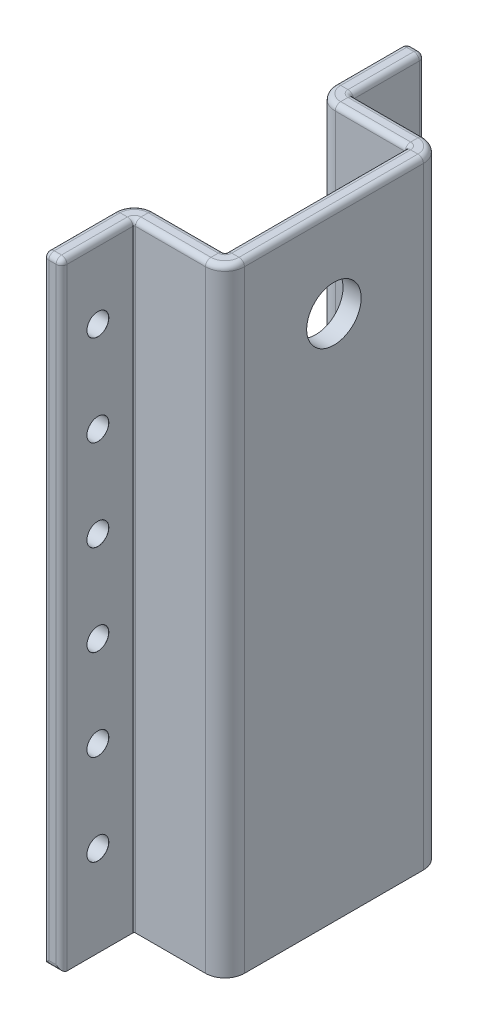
SolidWorks part; units mm, degrees
note: The reader was unsure of these and kept them because the rebuilt part matched: flange length of "Edge-Flange1", "Edge-Flange2".
material "1.0037 (S235JR)"
ref_plane "Front Plane" through (0, 0, 0) normal (0, 0, 1) x (1, 0, 0)
ref_plane "Top Plane" through (0, 0, 0) normal (0, 1, 0) x (1, 0, 0)
ref_plane "Right Plane" through (0, 0, 0) normal (1, 0, 0) x (0, 0, -1)
sketch "Sketch1" plane through (0, 0, 0) normal (1, 0, 0) x (0, 0, -1)
  line L1 (-60, 170) -> (60, 170)
  line L2 (-60, 170) -> (-60, -170)
  line L3 (-60, -170) -> (60, -170)
  line L4 (60, 170) -> (60, -170)
  point P6 (0, 170)
  point P7 (60, 0)
  dimension "D1" = 340
  dimension "D2" = 120
base flange "Base-Flange1" sketch "Sketch1" thickness 10 reverse thickness direction yes parameters "D1"=0.7366
edge flange "Edge-Flange1" sketch "Sketch10" flange profiles "Sketch10", "Sketch11" flange angle 90 flange length 60 flange position material inside bend radius 0.7366 thickness 10 relief rectangular parameters "D6"=10, "D8"=1
sketch "Sketch10" plane through (0, 0, 60) normal (0, 0, 1) x (0, 1, 0)
  line L2 (-170, 0) -> (-170, 50)
  line L3 (-170, 50) -> (170, 50)
  line L4 (170, 50) -> (170, 0)
  line L11 (170, 0) -> (-170, 0) construction
  line L12 (170, 0) -> (-170, 0)
sketch "Sketch11" plane through (0, 0, -60) normal (0, 0, -1) x (0, -1, 0)
  line L0 (170, 0) -> (-170, 0) construction
  line L1 (170, 0) -> (-170, 0)
  line L2 (-170, 0) -> (-170, 50)
  line L3 (-170, 50) -> (170, 50)
  line L4 (170, 50) -> (170, 0)
bend "EdgeBend1" bend radius 0.7366 bend angle 90 parameters "D5"=1
bend "EdgeBend2" bend radius 0.7366 bend angle 90 parameters "D5"=2
edge flange "Edge-Flange2" sketch "Sketch16" flange profiles "Sketch16", "Sketch17" flange angle 90 flange length 40 flange position material inside bend radius 0.7366 thickness 10 relief rectangular parameters "D6"=10, "D8"=1
sketch "Sketch16" plane through (-50, 0, 60) normal (-1, 0, 0) x (0, -1, 0)
  line L2 (-170, 0) -> (-170, 40)
  line L3 (-170, 40) -> (170, 40)
  line L4 (170, 40) -> (170, 0)
  line L7 (-170, 0) -> (170, 0) construction
  line L8 (-170, 0) -> (170, 0)
sketch "Sketch17" plane through (-50, 0, -60) normal (-1, 0, 0) x (0, 1, 0)
  line L0 (-170, 0) -> (170, 0) construction
  line L1 (-170, 0) -> (170, 0)
  line L2 (-170, 0) -> (-170, 40)
  line L3 (-170, 40) -> (170, 40)
  line L4 (170, 40) -> (170, 0)
bend "EdgeBend3" bend radius 0.7366 bend angle 90 parameters "D5"=3
bend "EdgeBend4" bend radius 0.7366 bend angle 90 parameters "D5"=4
sketch "Sketch18" plane through (10, 0, 0) normal (1, 0, 0) x (0, 0, -1)
  line L0 (-100, -170) -> (-100, 170) construction
  line L5 (49.2634, 170) -> (-49.2634, 170) construction
  circle A0 centre (0, 120) radius 15
  dimension "D1" = 30
  dimension "D3" = 100
  dimension "D2" = 50
extrude "Cut-Extrude1" cut sketch "Sketch18" against normal through all normal cut yes
hole_wizard "M10 Clearance Hole1" positions "Sketch19" profile "Sketch20" hole size "M10" standard "ANSI Metric" end condition through all
sketch "Sketch19" plane through (-40, 0, 0) normal (1, 0, 0) x (0, 0, -1)
  line L0 (100, 170) -> (100, -170) construction
  line L1 (100, -170) -> (60.7366, -170) construction
  point P0 (80, -120)
  point P2 (80, -70)
  point P4 (80, -20)
  point P6 (80, 30)
  point P8 (80, 80)
  point P10 (80, 130)
  dimension "D1" = 20
  dimension "D2" = 50
  dimension "D3" = 50
  dimension "D4" = 50
  dimension "D5" = 50
  dimension "D6" = 50
  dimension "D7" = 50
sketch "Sketch20" plane through (-40, -120, -80) normal (0, 1, 0) x (0, 0, -1)
  line L0 (0, 0) -> (0, 10)
  line L1 (0, 10) -> (6, 10)
  line L2 (6, 10) -> (6, 0.025)
  line L3 (6, 0.025) -> (6.025, 0)
  line L5 (6.025, 0) -> (0, 0)
  line L6 (-6, 0.025) -> (-6.025, 0) construction
  line L11 (0, -6.35) -> (0, 107.95) construction
  dimension "Thru Hole Dia." = 12
  dimension "Thru Hole Depth" = 10
  dimension "Near C'Sink Dia." = 12.05
  dimension "Near C'Sink Angle" = 90
mirror "Mirror1" about plane through (0, 0, 0) normal (0, 0, 1) of "M10 Clearance Hole1"
fillet "Fillet1" radius 3 26 edges at (-46.8553, 170, 53.1447) (-39.7843, 170, 60.2157) (-45, 170, 100) (-40, 170, 80.3683) (-50, 0, 100) (-50, 170, 80.3683) (-40, 0, 100) (-45, -170, 100) (-46.8553, 170, -53.1447) (-39.7843, 170, -60.2157) (-45, -170, -100) (-40, 170, -80.3683) (-50, 170, -80.3683) (-50, 0, -100) (-40, 0, -100) (-45, 170, -100) (0, 170, 0) (10, 170, 0) (6.8553, 170, 56.8553) (-0.2157, 170, 49.7843) (-20, 170, 50) (-20, 170, 60) (6.8553, 170, -56.8553) (-0.2157, 170, -49.7843) (-20, 170, -50) (-20, 170, -60)
sketch "Bend-Lines1" [suppressed] plane through (0, 0, 0) normal (0, 1, 0) x (1, 0, 0)
sketch "Bounding-Box1" [suppressed] plane through (0, 0, 0) normal (0, 1, 0) x (1, 0, 0)
sheet metal parameters "Sheet-Metal1" thickness 10 parameters "D1"=0.7366
flat pattern "Flat-Pattern1" [suppressed]
sketch "Bend-Lines2" plane through (0, 0, 0) normal (0, 1, 0) x (1, 0, 0)
sketch3d "Bounding-Box2" [suppressed]
  line L0 (75, 200, 0) -> (75, -200, 0) construction
  line L1 (-75, 200, 0) -> (-75, -200, 0) construction
  line L2 (75, 200, 0) -> (-75, 200, 0) construction
  line L3 (75, -200, 0) -> (-75, -200, 0) construction
sheet metal parameters "Sheet-Metal2" thickness 10 parameters "D1"=0.7366
flat pattern "Flat-Pattern1"
sketch "Bend-Lines2" plane through (0, 0, 0) normal (-1, 0, 0) x (0, 0, 1)
  line L0 (-68.7689, 200) -> (-68.7689, -200) construction
  line L1 (68.7689, -200) -> (68.7689, 200) construction
  line L2 (-68.7689, 200) -> (-68.7689, -200) construction
  line L3 (68.7689, -200) -> (68.7689, 200) construction
sketch3d "Bounding-Box2" [suppressed]
  line L0 (-137.5378, 200, 0) -> (-137.5378, -200, 0) construction
  line L1 (137.5378, 200, 0) -> (137.5378, -200, 0) construction
  line L2 (-137.5378, 200, 0) -> (137.5378, 200, 0) construction
  line L3 (-137.5378, -200, 0) -> (137.5378, -200, 0) construction
bend of the flat pattern "Flatten-<EdgeBend1>1"
bend of the flat pattern "Flatten-<EdgeBend2>1"
sheet metal parameters "Sheet-Metal3" thickness 10 parameters "D1"=0.7366
flat pattern "Flat-Pattern1"
sketch "Bend-Lines2" plane through (0, 0, 0) normal (-1, 0, 0) x (0, 0, 1)
  line L0 (-53.7689, 200) -> (-53.7689, -200) construction
  line L1 (53.7689, -200) -> (53.7689, 200) construction
  line L2 (-53.7689, 200) -> (-53.7689, -200) construction
  line L3 (53.7689, -200) -> (53.7689, 200) construction
  line L4 (-101.3067, 200) -> (-101.3067, -200) construction
  line L5 (101.3067, -200) -> (101.3067, 200) construction
  line L6 (-101.3067, 200) -> (-101.3067, -200) construction
  line L7 (101.3067, -200) -> (101.3067, 200) construction
sketch3d "Bounding-Box2" [suppressed]
  line L0 (-145.0757, 200, 0) -> (-145.0757, -200, 0) construction
  line L1 (145.0757, 200, 0) -> (145.0757, -200, 0) construction
  line L2 (-145.0757, 200, 0) -> (145.0757, 200, 0) construction
  line L3 (-145.0757, -200, 0) -> (145.0757, -200, 0) construction
bend of the flat pattern "Flatten-<EdgeBend1>1"
bend of the flat pattern "Flatten-<EdgeBend2>1"
bend of the flat pattern "Flatten-<EdgeBend3>1"
bend of the flat pattern "Flatten-<EdgeBend4>1"
sheet metal parameters "Sheet-Metal4" thickness 10 parameters "D1"=0.7366
flat pattern "Flat-Pattern1"
sketch "Bend-Lines2" plane through (0, 0, 0) normal (-1, 0, 0) x (0, 0, 1)
  line L0 (-53.7689, 170) -> (-53.7689, -170) construction
  line L1 (53.7689, -170) -> (53.7689, 170) construction
  line L2 (-53.7689, 170) -> (-53.7689, -170) construction
  line L3 (53.7689, -170) -> (53.7689, 170) construction
  line L4 (-101.3067, 170) -> (-101.3067, -170) construction
  line L5 (101.3067, -170) -> (101.3067, 170) construction
  line L6 (-101.3067, 170) -> (-101.3067, -170) construction
  line L7 (101.3067, -170) -> (101.3067, 170) construction
sketch3d "Bounding-Box2" [suppressed]
  line L0 (-145.0757, 170, 0) -> (-145.0757, -170, 0) construction
  line L1 (145.0757, 170, 0) -> (145.0757, -170, 0) construction
  line L2 (-145.0757, 170, 0) -> (145.0757, 170, 0) construction
  line L3 (-145.0757, -170, 0) -> (145.0757, -170, 0) construction
bend of the flat pattern "Flatten-<EdgeBend1>1"
bend of the flat pattern "Flatten-<EdgeBend2>1"
bend of the flat pattern "Flatten-<EdgeBend3>1"
bend of the flat pattern "Flatten-<EdgeBend4>1"
sheet metal parameters "Sheet-Metal7" thickness 10 parameters "D1"=0.7366
flat pattern "Flat-Pattern1"
sketch "Bend-Lines2" plane through (0, 0, 0) normal (-1, 0, 0) x (0, 0, 1)
  line L0 (-53.7689, 170) -> (-53.7689, -170) construction
  line L1 (53.7689, -170) -> (53.7689, 170) construction
  line L2 (-53.7689, 170) -> (-53.7689, -170) construction
  line L3 (53.7689, -170) -> (53.7689, 170) construction
  line L4 (-101.3067, 170) -> (-101.3067, -170) construction
  line L5 (101.3067, -170) -> (101.3067, 170) construction
  line L6 (-101.3067, 170) -> (-101.3067, -170) construction
  line L7 (101.3067, -170) -> (101.3067, 170) construction
sketch3d "Bounding-Box2" [suppressed]
  line L0 (-145.0757, 170, 0) -> (-145.0757, -170, 0) construction
  line L1 (145.0757, 170, 0) -> (145.0757, -170, 0) construction
  line L2 (-145.0757, 170, 0) -> (145.0757, 170, 0) construction
  line L3 (-145.0757, -170, 0) -> (145.0757, -170, 0) construction
bend of the flat pattern "Flatten-<EdgeBend1>1"
bend of the flat pattern "Flatten-<EdgeBend2>1"
bend of the flat pattern "Flatten-<EdgeBend3>1"
bend of the flat pattern "Flatten-<EdgeBend4>1"
sheet metal parameters "Sheet-Metal8" thickness 10 parameters "D1"=0.7366
flat pattern "Flat-Pattern1"
sketch "Bend-Lines2" plane through (0, 0, 0) normal (-1, 0, 0) x (0, 0, 1)
  line L0 (-53.7689, -170) -> (-53.7689, 167) construction
  line L1 (53.7689, -170) -> (53.7689, 167) construction
  line L2 (-53.7689, -170) -> (-53.7689, 167) construction
  line L3 (53.7689, -170) -> (53.7689, 167) construction
  line L4 (-101.3067, -170) -> (-101.3067, 167) construction
  line L5 (101.3067, -170) -> (101.3067, 167) construction
  line L6 (-101.3067, -170) -> (-101.3067, 167) construction
  line L7 (101.3067, -170) -> (101.3067, 167) construction
sketch3d "Bounding-Box2" [suppressed]
  line L0 (145.0757, 170, 0) -> (145.0757, -170, 0) construction
  line L1 (-145.0757, 170, 0) -> (-145.0757, -170, 0) construction
  line L2 (145.0757, 170, 0) -> (-145.0757, 170, 0) construction
  line L3 (145.0757, -170, 0) -> (-145.0757, -170, 0) construction
bend of the flat pattern "Flatten-<EdgeBend1>1"
bend of the flat pattern "Flatten-<EdgeBend2>1"
bend of the flat pattern "Flatten-<EdgeBend3>1"
bend of the flat pattern "Flatten-<EdgeBend4>1"
